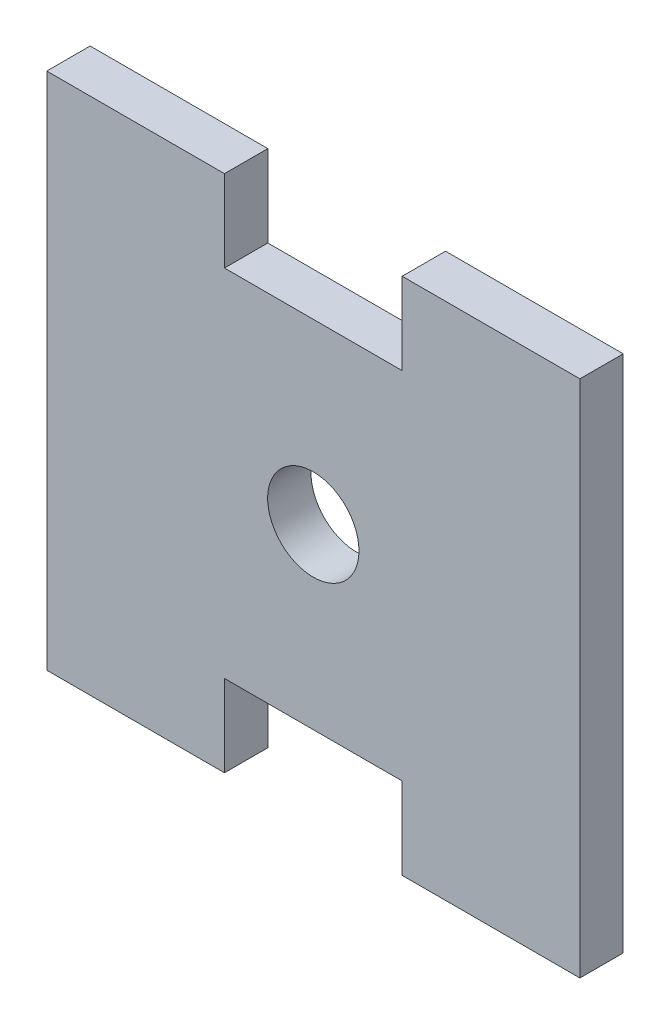
SolidWorks part; units mm, degrees
ref_plane "Front Plane" through (0, 0, 0) normal (0, 0, 1) x (1, 0, 0)
ref_plane "Top Plane" through (0, 0, 0) normal (0, 1, 0) x (1, 0, 0)
ref_plane "Right Plane" through (0, 0, 0) normal (1, 0, 0) x (0, 0, -1)
sketch "Sketch1" plane through (0, 0, 0) normal (0, 0, 1) x (1, 0, 0)
  line L0 (0, 12.7) -> (0, -12.7) construction
  line L1 (-6.35, -12.7) -> (6.35, -12.7)
  line L2 (-19.05, -12.7) -> (-19.05, 12.7)
  line L3 (-6.35, 12.7) -> (6.35, 12.7)
  line L4 (19.05, -12.7) -> (19.05, 12.7)
  line L5 (-19.05, -12.7) -> (19.05, 12.7) construction
  line L6 (-19.05, 12.7) -> (19.05, -12.7) construction
  line L7 (-19.05, 18.542) -> (-6.35, 18.542)
  line L8 (-19.05, 18.542) -> (-19.05, 12.7)
  line L9 (19.05, 18.542) -> (6.35, 12.7) construction
  line L10 (-6.35, 18.542) -> (-6.35, 12.7)
  line L11 (-19.05, 18.542) -> (-6.35, 12.7) construction
  line L12 (-19.05, 12.7) -> (-6.35, 18.542) construction
  line L13 (19.05, 12.7) -> (6.35, 18.542) construction
  line L14 (19.05, 18.542) -> (19.05, 12.7)
  line L15 (6.35, 18.542) -> (6.35, 12.7)
  line L16 (19.05, 18.542) -> (6.35, 18.542)
  line L17 (19.05, 0) -> (-19.05, 0) construction
  line L18 (-19.05, -18.542) -> (-19.05, -12.7)
  line L19 (-6.35, -18.542) -> (-6.35, -12.7)
  line L20 (-19.05, -12.7) -> (-6.35, -18.542) construction
  line L21 (-19.05, -18.542) -> (-6.35, -12.7) construction
  line L22 (-6.35, -12.7) -> (6.35, -12.7)
  line L23 (19.05, -18.542) -> (6.35, -12.7) construction
  line L24 (19.05, -12.7) -> (6.35, -18.542) construction
  line L25 (6.35, -18.542) -> (6.35, -12.7)
  line L26 (19.05, -18.542) -> (19.05, -12.7)
  line L27 (19.05, -18.542) -> (6.35, -18.542)
  line L28 (-19.05, -18.542) -> (-6.35, -18.542)
  circle A0 centre (0, 0) radius 3.2631
  point P0 (0, 0)
  point P8 (-12.7, 15.621)
  point P17 (12.7, 15.621)
  point P26 (12.7, -15.621)
  point P27 (-12.7, -15.621)
  dimension "D3" = 6.5262
  dimension "D1" = 25.4
  dimension "D2" = 38.1
  dimension "D4" = 5.842
  dimension "D5" = 12.7
extrude "Boss-Extrude1" add sketch "Sketch1" along normal blind 3.0988 contours L18 L28 L19 L1 L25 L27 L26 L4 L14 L16 L15 L3 L10 L7 L8 L2 A0 region at (-6.8817, -15.621, 0)
